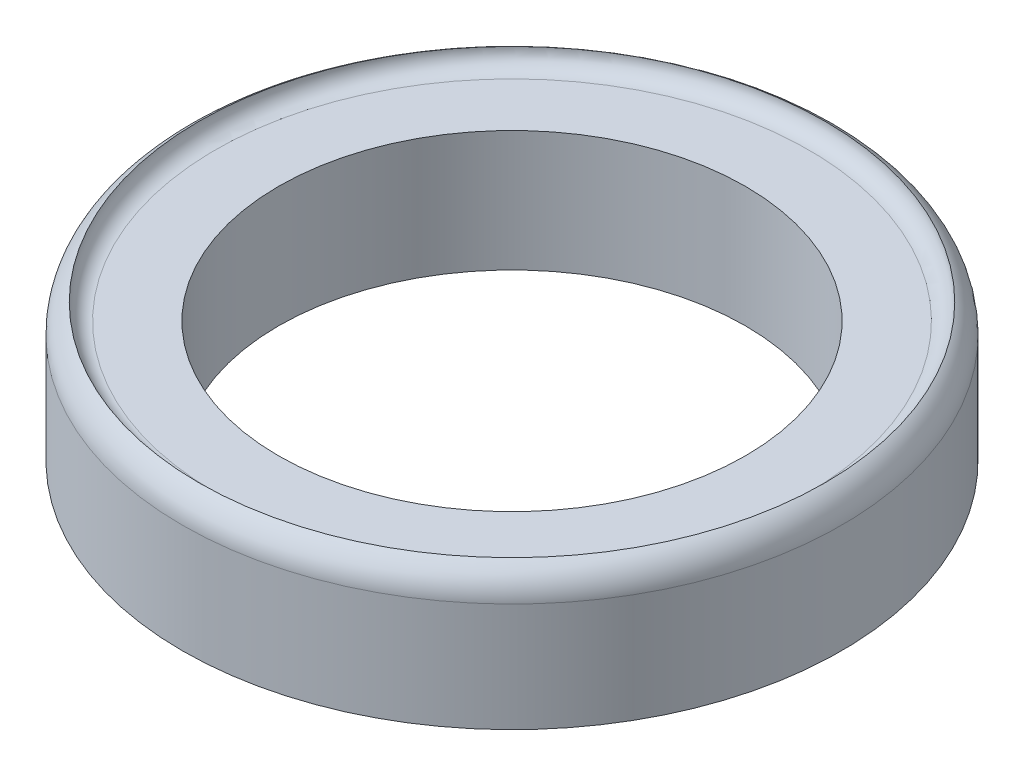
SolidWorks part; units mm, degrees
ref_plane "Front Plane" through (0, 0, 0) normal (0, 0, 1) x (1, 0, 0)
ref_plane "Top Plane" through (0, 0, 0) normal (0, 1, 0) x (1, 0, 0)
ref_plane "Right Plane" through (0, 0, 0) normal (1, 0, 0) x (0, 0, -1)
sketch "Sketch1" plane through (0, 0, 0) normal (0, 1, 0) x (1, 0, 0)
  line L0 (-24, 0) -> (-22.8, 0)
  line L2 (22.8, 0) -> (24, 0)
  circle A0 centre (0, 0) radius 24
  circle A1 centre (0, 0) radius 22.8
  circle A2 centre (0, 0) radius 17
  dimension "D1" = 48
  dimension "D2" = 45.6
  dimension "D3" = 34
extrude "Boss-Extrude4" add sketch "Sketch1" along normal blind 8.8 contours A1 A2 region at (0, 0, -22.1551)
extrude "Boss-Extrude6" add sketch "Sketch1<7>" along normal blind 10 contours A1 L0 A0 L2 | A1 L2 A0 L0 region at (0, 0, -23.4633) region at (-23.4, 0, 0.5367)
sketch "Sketch1<7>" plane through (0, 0, 0) normal (0, 1, 0) x (1, 0, 0) same geometry as "Sketch1"
fillet "Fillet1" radius 1.2 1 edges at (0, 8.8, 22.8)
fillet "Fillet2" radius 2.4 1 edges at (0, 10, 24)
